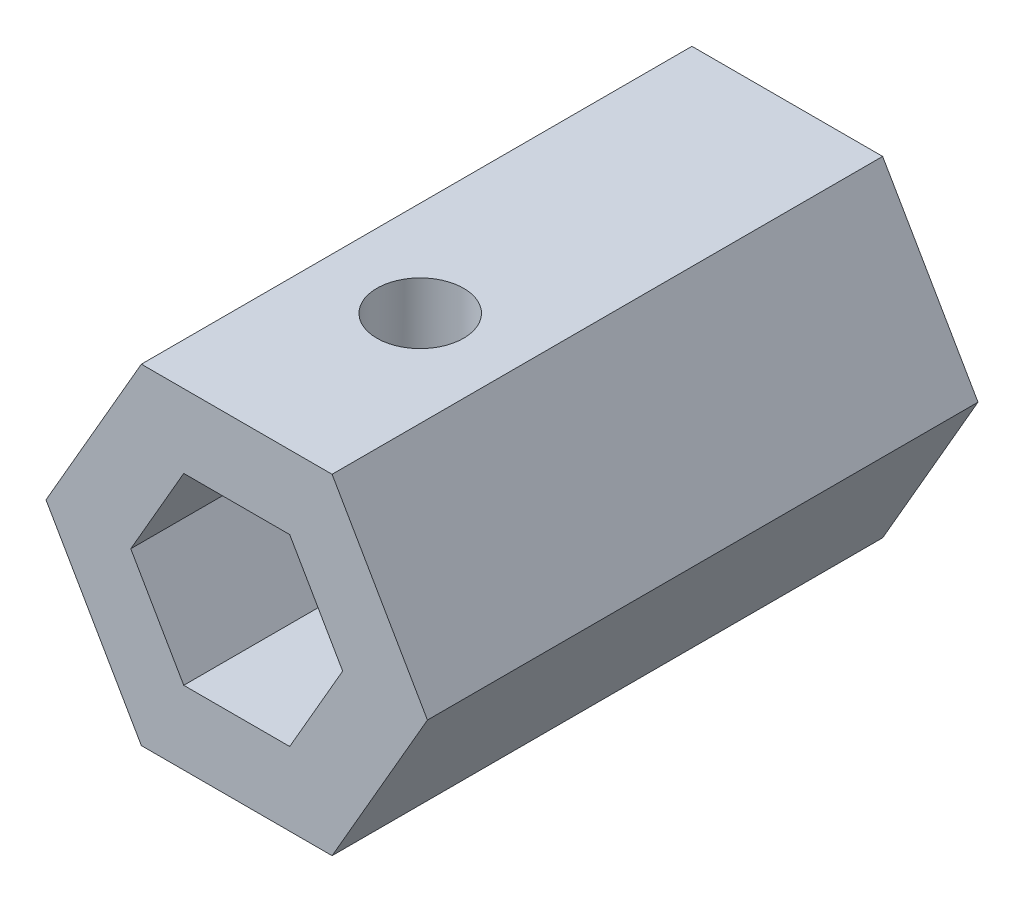
SolidWorks part; units mm, degrees
material "ABS"
ref_plane "Front Plane" through (0, 0, 0) normal (0, 0, 1) x (1, 0, 0)
ref_plane "Top Plane" through (0, 0, 0) normal (0, 1, 0) x (1, 0, 0)
ref_plane "Right Plane" through (0, 0, 0) normal (1, 0, 0) x (0, 0, -1)
sketch "Sketch1" plane through (0, 0, 0) normal (0, 0, 1) x (1, 0, 0)
  line L0 (6.5991, 11.43) -> (-6.5991, 11.43)
  line L1 (3.6662, -6.35) -> (7.3323, 0)
  line L2 (7.3323, 0) -> (3.6662, 6.35)
  line L3 (3.6662, 6.35) -> (-3.6662, 6.35)
  line L4 (-3.6662, 6.35) -> (-7.3323, 0)
  line L5 (-7.3323, 0) -> (-3.6662, -6.35)
  line L6 (-3.6662, -6.35) -> (3.6662, -6.35)
  line L7 (-6.5991, 11.43) -> (-13.1982, 0)
  line L8 (-13.1982, 0) -> (-6.5991, -11.43)
  line L9 (-6.5991, -11.43) -> (6.5991, -11.43)
  line L10 (6.5991, -11.43) -> (13.1982, 0)
  line L11 (13.1982, 0) -> (6.5991, 11.43)
  circle A0 centre (0, 0) radius 6.35 construction
  point P16 (0, 0)
  dimension "D1" = 12.7
  dimension "D2" = 5.08
extrude "Boss-Extrude1" add sketch "Sketch1" along normal blind 2.54 contours L5 L6 L1 L2 L3 L4 | L10 L11 L0 L7 L8 L9 L6 L5 L4 L3 L2 L1 region at (9.5963, 5.5404, 0) region at (0, 0, 0)
sketch "Sketch2" plane through (0, 0, 2.54) normal (0, 0, 1) x (1, 0, 0)
  point P0 (0, 0)
  point P1 (-17.2019, 6.9381)
hole_wizard "CSK for #8 Flat Head Machine Screw (100)1" positions "Sketch2" profile "Sketch3" countersink size "#8" standard "ANSI Inch" end condition through all
sketch "Sketch3" plane through (0, 0, 2.54) normal (1, 0, 0) x (0, -1, 0)
  line L0 (0, 0) -> (0, 2.54)
  line L1 (0, 2.54) -> (2.2479, 2.54)
  line L2 (2.2479, 2.54) -> (2.2479, 1.6518)
  line L3 (2.2479, 1.6518) -> (4.2164, 0)
  line L5 (4.2164, 0) -> (0, 0)
  line L6 (-2.2479, 1.6518) -> (-4.2164, 0) construction
  line L11 (0, -6.35) -> (0, 107.95) construction
  dimension "Thru Hole Dia." = 4.4958
  dimension "Thru Hole Depth" = 2.54
  dimension "Near C'Sink Dia." = 8.4328
  dimension "Near C'Sink Angle" = 100
extrude "Boss-Extrude2" add sketch "Sketch1<4>" along normal blind 25.4
sketch "Sketch1<4>" plane through (0, 0, 0) normal (0, 0, 1) x (1, 0, 0) same geometry as "Sketch1"
sketch "Sketch4" plane through (0, 11.43, 0) normal (0, 1, 0) x (1, 0, 0)
  line L0 (0, 0) -> (0, -25.4) construction
  line L1 (6.5991, 0) -> (-6.5991, 0) construction
  line L2 (6.5991, -25.4) -> (-6.5991, -25.4) construction
  point P6 (0, -12.7)
hole_wizard "M7x1.0 Tapped Hole1" positions "Sketch4" profile "Sketch5" tap size "M7x1.0" standard "ANSI Metric" end condition through all
sketch "Sketch5" plane through (0, 11.43, 12.7) normal (1, 0, 0) x (0, 0, 1)
  line L0 (0, 0) -> (0, 22.86)
  line L1 (0, 22.86) -> (3, 22.86)
  line L2 (3, 22.86) -> (3, 0)
  line L5 (3, 0) -> (0, 0)
  line L11 (0, -6.35) -> (0, 107.95) construction
  dimension "Thru Tap Drill Dia." = 6
  dimension "Thru Tap Drill Depth" = 22.86
cosmetic thread "Hole Thread2" parameters "D2"=7
sketch "Sketch6" plane through (0, 0, 0) normal (0, 0, -1) x (-1, 0, 0)
  line L6 (-13.1982, 0) -> (-6.5991, -11.43)
  line L7 (-6.5991, -11.43) -> (6.5991, -11.43)
  line L8 (6.5991, -11.43) -> (13.1982, 0)
  line L9 (13.1982, 0) -> (6.5991, 11.43)
  line L10 (6.5991, 11.43) -> (-6.5991, 11.43)
  line L11 (-6.5991, 11.43) -> (-13.1982, 0)
  line L12 (-13.1982, 0) -> (-6.5991, -11.43)
  line L13 (-6.5991, -11.43) -> (6.5991, -11.43)
  line L14 (6.5991, -11.43) -> (13.1982, 0)
  line L15 (13.1982, 0) -> (6.5991, 11.43)
  line L16 (6.5991, 11.43) -> (-6.5991, 11.43)
  line L17 (-6.5991, 11.43) -> (-13.1982, 0)
  circle A0 centre (0, 0) radius 6.05
  dimension "D2" = 12.1
  dimension "D1" = 0
extrude "Boss-Extrude3" add sketch "Sketch6" along normal blind 12.7
